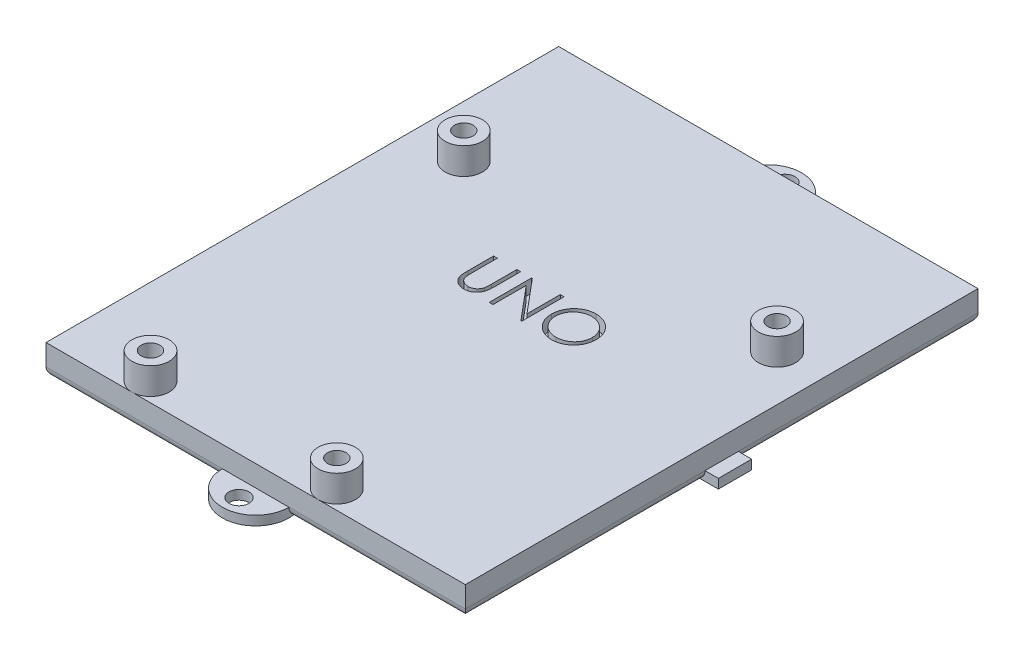
SolidWorks part; units mm, degrees
ref_plane "Front Plane" through (0, 0, 0) normal (0, 0, 1) x (1, 0, 0)
ref_plane "Top Plane" through (0, 0, 0) normal (0, 1, 0) x (1, 0, 0)
ref_plane "Right Plane" through (0, 0, 0) normal (1, 0, 0) x (0, 0, -1)
sketch "Sketch1" plane through (0, 0, 0) normal (0, 1, 0) x (1, 0, 0)
  line L0 (-31.45, 38.45) -> (31.45, 38.45)
  line L5 (-31.45, 38.45) -> (-31.45, -38.45)
  line L6 (-31.45, -38.45) -> (31.45, -38.45)
  line L7 (31.45, 38.45) -> (31.45, -38.45)
  point P11 (-31.45, 0)
  point P12 (0, -38.45)
  dimension "D3" = 76.9
  dimension "D4" = 62.9
extrude "Boss-Extrude1" add sketch "Sketch1" along normal blind 4.575
sketch "Sketch2" plane through (0, 4.575, 0) normal (0, 1, 0) x (1, 0, 0)
  line L0 (9.37, -35.65) -> (9.37, 15.15) construction
  line L1 (24.61, 15.15) -> (9.37, 15.15) construction
  line L2 (9.37, -35.65) -> (-18.57, -35.65) construction
  line L3 (-18.57, -35.65) -> (-18.57, 16.42) construction
  line L4 (0, -38.45) -> (0, 38.45) construction
  line L5 (-31.45, 0) -> (31.45, 0) construction
  line L6 (-18.57, 16.42) -> (-23.65, 16.42) construction
  line L11 (-31.45, 38.45) -> (-31.45, -38.45) construction
  line L12 (-31.45, -38.45) -> (31.45, -38.45) construction
  line L13 (31.45, 38.45) -> (-31.45, 38.45) construction
  line L14 (31.45, -38.45) -> (31.45, 38.45) construction
  circle A0 centre (9.37, -35.65) radius 2.8
  circle A1 centre (24.61, 15.15) radius 2.8
  circle A2 centre (-23.65, 16.42) radius 2.8
  circle A3 centre (-18.57, -35.65) radius 2.8
  circle A4 centre (24.61, 15.15) radius 1.4
  circle A5 centre (9.37, -35.65) radius 1.4
  circle A6 centre (-18.57, -35.65) radius 1.4
  circle A7 centre (-23.65, 16.42) radius 1.4
  dimension "D7" = 2.8
  dimension "D10" = 1.4
  dimension "D6" = 7.8
  dimension "D1" = 27.94
  dimension "D2" = 15.24
  dimension "D3" = 5.08
  dimension "D4" = 1.27
  dimension "D5" = 50.8
extrude "Boss-Extrude2" add sketch "Sketch2" along normal blind 4
sketch "Sketch3" plane through (0, 4.575, 0) normal (0, 1, 0) x (1, 0, 0)
  circle A0 centre (9.37, -35.65) radius 1.4
  circle A1 centre (-18.57, -35.65) radius 1.4
  circle A2 centre (-23.65, 16.42) radius 1.4
  circle A3 centre (24.61, 15.15) radius 1.4
  circle A4 centre (24.61, 15.15) radius 1.4 construction
  circle A5 centre (-23.65, 16.42) radius 1.4 construction
extrude "Cut-Extrude1" cut sketch "Sketch3" against normal offset from surface (3.575 mm away) 1 up to face at (0, 0, 0)
sketch "Sketch4" plane through (0, 0, 0) normal (0, 1, 0) x (1, 0, 0)
  line L0 (-5, -38.45) -> (5, -38.45)
  line L3 (-31.45, -38.45) -> (31.45, -38.45) construction
  line L4 (0, -38.45) -> (0, -43.45) construction
  arc A0 (-5, -38.45) -> (5, -38.45) centre (0, -38.45) ccw
  circle A2 centre (0, -40.95) radius 1.5
  point P6 (0, -38.45)
  dimension "D2" = 3
  dimension "D3" = 5
extrude "Boss-Extrude3" add sketch "Sketch4" along normal blind 1.4
mirror "Mirror1" about plane through (0, 0, 0) normal (0, 0, 1) of "Boss-Extrude3"
sketch "Sketch5" plane through (0, 4.575, 0) normal (0, 1, 0) x (1, 0, 0)
  line L0 (-15, 0) -> (15, 0) construction
  text T0 "UNO" font "Century Gothic" height in points 24
  point P6 (0, 0)
  dimension "D1" = 30
extrude "Cut-Extrude2" cut sketch "Sketch5" against normal blind 2
sketch "Sketch6" plane through (-31.45, 0, 0) normal (-1, 0, 0) x (0, 0, 1)
  line L0 (-38.45, 0) -> (38.45, 0) construction
  line L1 (-2.5, 0) -> (2.5, 0)
  line L2 (-2.5, 0) -> (-2.5, 1.4)
  line L3 (-2.5, 1.4) -> (2.5, 1.4)
  line L4 (2.5, 0) -> (2.5, 1.4)
  line L5 (43.45, 1.4) -> (38.45, 1.4) construction
  point P6 (0, 0)
  point P7 (0, 1.4)
  dimension "D1" = 5
extrude "Boss-Extrude4" add sketch "Sketch6" along normal blind 2
mirror "Mirror2" about plane through (0, 0, 0) normal (1, 0, 0) of "Boss-Extrude4"
fillet "Fillet1" radius 1.4 8 edges at (-18.225, 0, 38.45) (18.225, 0, 38.45) (31.45, 0, -20.475) (31.45, 0, 20.475) (18.225, 0, -38.45) (-18.225, 0, -38.45) (-31.45, 0, 20.475) (-31.45, 0, -20.475)
